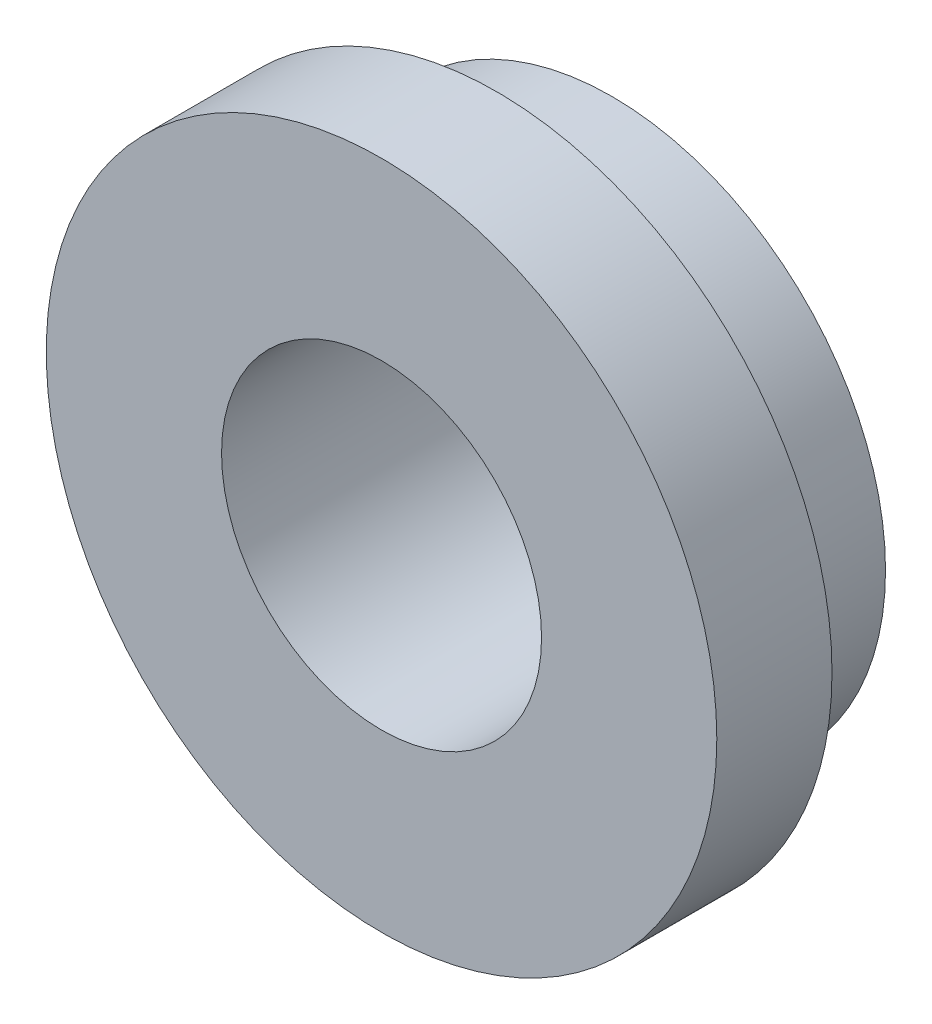
SolidWorks part; units mm, degrees
ref_plane "Front Plane" through (0, 0, 0) normal (0, 0, 1) x (1, 0, 0)
ref_plane "Top Plane" through (0, 0, 0) normal (0, 1, 0) x (1, 0, 0)
ref_plane "Right Plane" through (0, 0, 0) normal (1, 0, 0) x (0, 0, -1)
sketch "Sketch1" plane through (0, 0, 0) normal (0, 0, 1) x (1, 0, 0)
  circle A0 centre (0, 0) radius 14.25
  dimension "D1" = 28.5
extrude "Boss-Extrude1" add sketch "Sketch1" along normal blind 6 contours A0
sketch "Sketch2" plane through (0, 0, 6) normal (0, 0, 1) x (1, 0, 0)
  circle A0 centre (0, 0) radius 17.4625
  dimension "D1" = 34.925
extrude "Boss-Extrude2" add sketch "Sketch2" along normal blind 6
hole_wizard "5/8 Clearance Hole1" positions "Sketch3" profile "Sketch5" hole size "5/8" standard "ANSI Inch" end condition through all
sketch "Sketch3" plane through (0, 0, 12) normal (0, 0, 1) x (1, 0, 0)
  point P0 (0, 0)
sketch "Sketch5" plane through (0, 0, 12) normal (1, 0, 0) x (0, -1, 0)
  line L0 (0, 0) -> (0, 12)
  line L1 (0, 12) -> (8.3337, 12)
  line L2 (8.3337, 12) -> (8.3337, 0)
  line L5 (8.3337, 0) -> (0, 0)
  line L11 (0, -6.35) -> (0, 107.95) construction
  dimension "Thru Hole Dia." = 16.6675
  dimension "Thru Hole Depth" = 12
